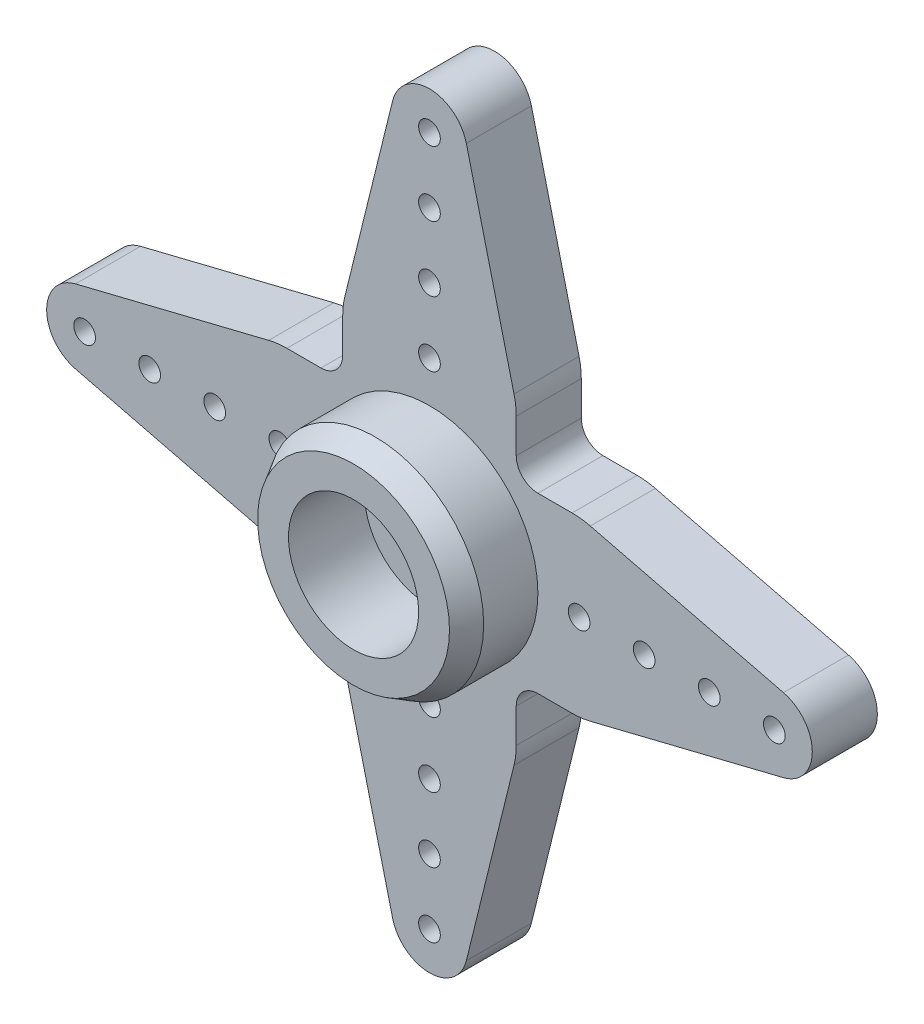
SolidWorks part; units mm, degrees
material "Nylon 101"
ref_plane "Front Plane" through (0, 0, 0) normal (0, 0, 1) x (1, 0, 0)
ref_plane "Top Plane" through (0, 0, 0) normal (0, 1, 0) x (1, 0, 0)
ref_plane "Right Plane" through (0, 0, 0) normal (1, 0, 0) x (0, 0, -1)
ref_axis "Axis1" through (0, 0, -0.15) along (0, 0, 1)
sketch "Sketch1" plane through (0, 0, 0) normal (0, 0, 1) x (1, 0, 0)
  line L0 (-4, 0) -> (-4, 6.5743)
  line L1 (-3.898, 7.4133) -> (-1.699, 16.3191)
  line L2 (1.699, 16.3191) -> (3.898, 7.4133)
  line L3 (4, 6.5743) -> (4, 0)
  line L4 (4, 0) -> (1.25, 0)
  line L5 (-4, 0) -> (-1.25, 0)
  line L6 (0, 0) -> (0, 23.2) construction
  arc A0 (1.25, 0) -> (-1.25, 0) centre (0, 0) ccw
  arc A1 (-1.699, 16.3191) -> (1.699, 16.3191) centre (0, 15.8996) cw
  arc A2 (-4, 6.5743) -> (-3.898, 7.4133) centre (-0.5, 6.5743) cw
  arc A3 (3.898, 7.4133) -> (4, 6.5743) centre (0.5, 6.5743) cw
  dimension "D1" = 1.25
  dimension "D4" = 1.75
  dimension "D5" = 3.5
  dimension "D6" = 6.5743
  dimension "D2" = 8
  dimension "D3" = 23.2
extrude "Boss-Extrude1" add sketch "Sketch1" along normal blind 3
hole_wizard "Ø1.0mm Dowel Hole1" positions "Sketch4" profile "Sketch5" hole size "Ø1.0" standard "ANSI Metric" end condition up to next
sketch "Sketch4" plane through (0, 0, 3) normal (0, 0, 1) x (1, 0, 0)
  point P0 (0, 15.8996)
sketch "Sketch5" plane through (0, 15.8996, 3) normal (1, 0, 0) x (0, -1, 0)
  line L0 (0, 0) -> (0, 3.001)
  line L1 (0, 3.001) -> (0.5, 3.001)
  line L2 (0.5, 3.001) -> (0.5, 0)
  line L5 (0.5, 0) -> (0, 0)
  line L11 (0, -6.35) -> (0, 107.95) construction
  dimension "Thru Hole Dia." = 1
  dimension "Thru Hole Depth" = 3.001
pattern_linear "LPattern1" count 4 spacing 3 along (0, -1, 0) of "Ø1.0mm Dowel Hole1"
pattern_circular "CirPattern1" count 4 over 360 about axis through (0, 0, -0.15) along (0, 0, 1) of "LPattern1", "Ø1.0mm Dowel Hole1", "Boss-Extrude1"
sketch "Sketch6" plane through (0, 0, 3) normal (0, 0, 1) x (1, 0, 0)
  circle A0 centre (0, 0) radius 3
  circle A1 centre (0, 0) radius 5
  dimension "D1" = 6
  dimension "D2" = 10
extrude "Boss-Extrude2" add sketch "Sketch6" along normal blind 3.5
chamfer "Chamfer1" distance 1 angle 30 1 edges at (5, 0, 6.5) first distance on face at (5, 0, 6.5)
fillet "Fillet1" radius 1 4 edges at (-4, 4, 1.5) (-4, -4, 1.5) (4, -4, 1.5) (4, 4, 1.5)
